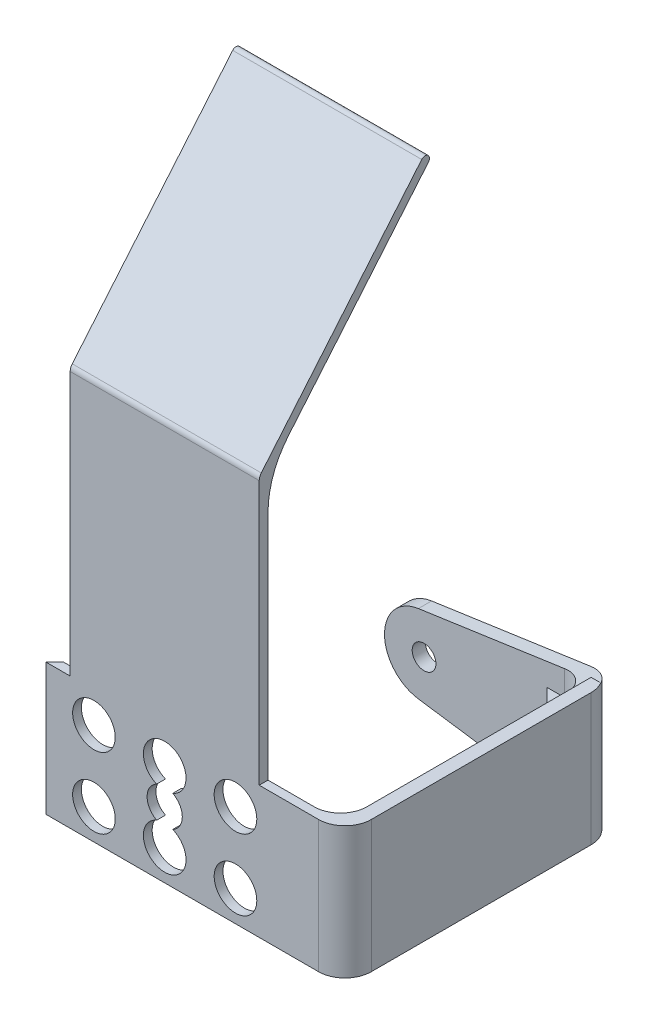
SolidWorks part; units mm, degrees
ref_plane "前视基准面" through (0, 0, 0) normal (0, 0, 1) x (1, 0, 0)
ref_plane "上视基准面" through (0, 0, 0) normal (0, 1, 0) x (1, 0, 0)
ref_plane "右视基准面" through (0, 0, 0) normal (1, 0, 0) x (0, 0, -1)
sketch "草图1" plane through (0, 0, 0) normal (0, 0, 1) x (1, 0, 0)
  line L1 (-13.5, -7.5) -> (13.5, -7.5)
  line L2 (-13.5, -7.5) -> (-13.5, 7.5)
  line L3 (-13.5, 7.5) -> (13.5, 7.5)
  line L4 (13.5, -7.5) -> (13.5, 7.5)
  line L5 (-13.5, -7.5) -> (13.5, 7.5) construction
  line L6 (-13.5, 7.5) -> (13.5, -7.5) construction
  point P0 (0, 0)
  dimension "D1" = 27
  dimension "D2" = 15
extrude "凸台-拉伸1" add sketch "草图1" along normal blind 1
sketch "草图2" plane through (0, 0, 1) normal (0, 0, 1) x (1, 0, 0)
  line L0 (-8.05, 4.025) -> (8.05, 4.025) construction
  line L3 (0, 1.6) -> (0, -1.6) construction
  line L4 (8.05, 4.025) -> (8.05, -4.025) construction
  line L5 (8.05, -4.025) -> (-8.05, -4.025) construction
  line L6 (-8.05, -4.025) -> (-8.05, 4.025) construction
  circle A0 centre (0, 4.025) radius 2.425
  circle A1 centre (0, -4.025) radius 2.425
  circle A2 centre (8.05, 4.025) radius 2.425
  circle A3 centre (8.05, -4.025) radius 2.425
  circle A4 centre (-8.05, 4.025) radius 2.425
  circle A5 centre (-8.05, -4.025) radius 2.425
  point P2 (0, 1.6)
  point P5 (0, -1.6)
  point P6 (0, 0)
  point P11 (-2.425, 4.025)
  point P20 (-5.625, 4.025)
  dimension "D1" = 4.85
  dimension "D4" = 3.2
  dimension "D2" = 3.2
extrude "切除-拉伸1" cut sketch "草图2" against normal through all
sketch "草图3" plane through (0, -7.5, 0) normal (0, -1, 0) x (1, 0, 0)
  line L0 (13.5, 0) -> (19, 0)
  line L1 (13.5, 1) -> (13.5, 0)
  line L2 (20.5, 1) -> (13.5, 1)
  line L3 (20.5, 1) -> (20.5, -30)
  line L5 (19, -28.5) -> (19, 0)
  line L6 (-4.5, -28.5) -> (-4.5, -30)
  line L7 (-4.5, -30) -> (20.5, -30)
  line L9 (-4.5, -28.5) -> (19, -28.5)
  dimension "D1" = 7
  dimension "D2" = 1.5
  dimension "D3" = 1.5
  dimension "D4" = 30
  dimension "D5" = 25
extrude "凸台-拉伸2" add sketch "草图3" against normal up to surface (15 mm away) up to face at (0, 7.5, 0.5)
sketch "草图6" plane through (0, 0, 0) normal (0, 1, 0) x (1, 0, 0)
  line L0 (19, 0) -> (19, 5)
  line L1 (19, 28.5) -> (19, 0) construction
  line L2 (19, 5) -> (14, 0)
  line L3 (19, 0) -> (-13.5, 0) construction
  line L4 (14, 0) -> (19, 0)
  line L5 (19, 28.5) -> (14, 28.5)
  line L6 (-4.5, 28.5) -> (19, 28.5) construction
  line L7 (14, 28.5) -> (19, 23.5)
  line L8 (19, 23.5) -> (19, 28.5)
  line L9 (20.5, 30) -> (-4.5, 30) construction
  line L10 (19, 19) -> (17.5, 19)
  line L11 (19, 19) -> (19, 21)
  line L12 (19, 21) -> (17.5, 21)
  line L13 (17.5, 19) -> (17.5, 21)
  point P18 (17.5, 20)
  dimension "D1" = 5
  dimension "D2" = 5
  dimension "D3" = 5
  dimension "D4" = 5
  dimension "D5" = 10
  dimension "D6" = 1.5
  dimension "D7" = 2
extrude "凸台-拉伸3" add sketch "草图6" along normal mid plane 8
sketch "草图7" plane through (0, 0, -30) normal (0, 0, -1) x (-1, 0, 0)
  line L0 (0.6417, -4.454) -> (-20.5, -7.5)
  line L1 (-20.5, 7.5) -> (-20.5, -7.5) construction
  line L2 (4.5, -7.5) -> (-20.5, -7.5) construction
  line L3 (-20.5, -7.5) -> (-20.5, 7.5)
  line L4 (-20.5, 7.5) -> (0.6417, 4.454)
  line L5 (4.5, -7.5) -> (-20.5, -7.5)
  line L6 (4.5, -7.5) -> (4.5, 7.5)
  line L7 (4.5, 7.5) -> (-20.5, 7.5)
  circle A0 centre (0, 0) radius 1.35
  circle A1 centre (0, 0) radius 4.5
  line M3 (4.5, 7.5) -> (-20.5, 7.5)
  line M5 (-20.5, -7.5) -> (4.5, -7.5)
  line M6 (4.5, -7.5) -> (4.5, 7.5)
  dimension "D1" = 2.7
extrude "切除-拉伸3" cut sketch "草图7" against normal up to surface (1.5 mm away) contours A1 L0 M5 M6 | A1 L6 L4 M3 | A0 region at (3.353, -6.0984, -30) region at (3.353, 6.0984, -30) region at (0, 0, -30) up to face at (11.875, 0, -28.5)
fillet "圆角1" radius 3 6 edges at (20.5, 0, -30) (20.5, 0, 1) (19, 5.75, 0) (19, -5.75, 0) (19, 5.6419, -28.5) (19, -5.6419, -28.5)
chamfer "倒角1" distance 1 angle 45 1 edges at (-13.5, 0, 0)
sketch "草图8" plane through (0, 0, 0) normal (0, 0, -1) x (-1, 0, 0)
  circle A0 centre (0, 0) radius 2
  dimension "D1" = 4
extrude "切除-拉伸4" cut sketch "草图8" against normal up to next
sketch "草图9" plane through (0, 0, 1) normal (0, 0, 1) x (1, 0, 0)
  line L0 (0, 0) -> (0, 32.1698) construction
  line L1 (17.5, 7.5) -> (-13.5, 7.5) construction
  line L2 (10.75, 37.5) -> (-10.75, 37.5)
  line L3 (10.75, 37.5) -> (10.75, 7.5)
  line L4 (10.75, 7.5) -> (-10.75, 7.5)
  line L5 (-10.75, 37.5) -> (-10.75, 7.5)
  line L6 (10.75, 37.5) -> (-10.75, 7.5) construction
  line L7 (10.75, 7.5) -> (-10.75, 37.5) construction
  point P3 (0, 22.5)
  dimension "D1" = 30
  dimension "D2" = 21.5
extrude "凸台-拉伸4" add sketch "草图9" against normal up to surface (1 mm away) up to face at (0, 0, 0)
sketch "草图10" plane through (0, 0, 0) normal (1, 0, 0) x (0, 0, -1)
  line L0 (0, 37.5) -> (25, 67.2938)
  line L1 (25, 67.2938) -> (24.234, 67.9366) construction
  line L2 (24.234, 67.9366) -> (-0.766, 38.1428)
  line L4 (-1, 37.5) -> (25, 37.5) construction
  line L5 (25, 37.5) -> (25, 67.2938) construction
  line L6 (-1, 37.5) -> (0, 37.5)
  line L7 (18.5721, 59.6334) -> (17.8061, 60.2762)
  line L8 (30, 7.0678) -> (30, 4.454) construction
  arc A0 (-0.766, 38.1428) -> (-1, 37.5) centre (0, 37.5) ccw
  dimension "D1" = 40
  dimension "D2" = 5
  dimension "D3" = 10
extrude "凸台-拉伸5" add sketch "草图10" against normal up to surface and the other way up to surface contours L2 A0 L6 L0 L7 region at (0, 48.7548, -8.7894) up to face at (-10.75, 22.5, 0.5) other way up to face at (10.75, 22.5, 0.5)
fillet "圆角2" radius 10 1 edges at (0, 37.5, 0)
fillet "圆角3" radius 0.5 2 edges at (0, 60.2762, -17.8061) (0, 59.6334, -18.5721)
